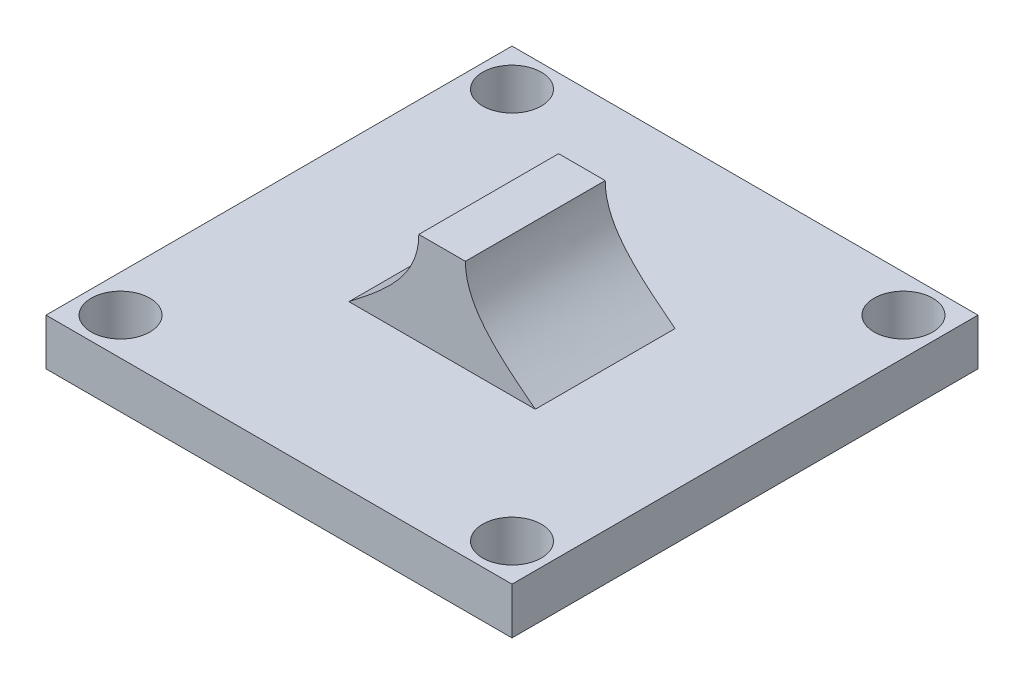
SolidWorks part; units mm, degrees
ref_plane "Front Plane" through (0, 0, 0) normal (0, 0, 1) x (1, 0, 0)
ref_plane "Top Plane" through (0, 0, 0) normal (0, 1, 0) x (1, 0, 0)
ref_plane "Right Plane" through (0, 0, 0) normal (1, 0, 0) x (0, 0, -1)
sketch "Sketch1" plane through (0, 0, 0) normal (0, 1, 0) x (1, 0, 0)
  line L1 (-25, 25) -> (25, 25)
  line L2 (-25, 25) -> (-25, -25)
  line L3 (-25, -25) -> (25, -25)
  line L4 (25, 25) -> (25, -25)
  line L5 (-25, 25) -> (25, -25) construction
  line L6 (-25, -25) -> (25, 25) construction
  point P0 (0, 0)
  dimension "D1" = 50
  dimension "D2" = 50
extrude "Boss-Extrude1" add sketch "Sketch1" along normal blind 5
sketch "Sketch2" plane through (0, 5, 0) normal (0, 1, 0) x (1, 0, 0)
  line L1 (-10, 7.5) -> (10, 7.5)
  line L2 (-10, 7.5) -> (-10, -7.5)
  line L3 (-10, -7.5) -> (10, -7.5)
  line L4 (10, 7.5) -> (10, -7.5)
  line L5 (-10, 7.5) -> (10, -7.5) construction
  line L6 (-10, -7.5) -> (10, 7.5) construction
  point P0 (0, 0)
  dimension "D1" = 20
  dimension "D2" = 15
ref_plane "Plane1" through (0, 15, 0) normal (0, 1, 0) x (1, 0, 0)
sketch "Sketch3" plane through (0, 15, 0) normal (0, 1, 0) x (1, 0, 0)
  line L0 (-10, -7.5) -> (10, -7.5) construction
  line L1 (-2.5, 7.5) -> (2.5, 7.5)
  line L2 (-2.5, 7.5) -> (-2.5, -7.5)
  line L3 (-2.5, -7.5) -> (2.5, -7.5)
  line L4 (2.5, 7.5) -> (2.5, -7.5)
  line L5 (-2.5, 7.5) -> (2.5, -7.5) construction
  line L6 (-2.5, -7.5) -> (2.5, 7.5) construction
  point P0 (0, 0)
  dimension "D1" = 5
loft "Loft1" add profiles "Sketch3", "Sketch2" start constraint normal to profile start tangent length 1 connector at (-2.5, 15, -7.5) connector at (-10, 5, -7.5)
sketch "Sketch7" plane through (0, 0, 0) normal (0, -1, 0) x (-1, 0, 0)
  line L0 (25, 25) -> (25, -25) construction
  line L1 (25, -25) -> (-25, -25) construction
  line L2 (-25, -25) -> (-25, 25) construction
  line L3 (-25, 25) -> (25, 25) construction
  circle A0 centre (21, -21) radius 3.15
  circle A1 centre (-21, -21) radius 3.15
  circle A2 centre (-21, 21) radius 3.15
  circle A3 centre (21, 21) radius 3.15
  dimension "D1" = 6.3
  dimension "D2" = 6.3
  dimension "D3" = 6.3
  dimension "D4" = 6.3
  dimension "D5" = 4
  dimension "D6" = 4
  dimension "D7" = 4
  dimension "D8" = 4
  dimension "D9" = 4
  dimension "D10" = 4
  dimension "D11" = 4
  dimension "D12" = 4
extrude "Cut-Extrude1" cut sketch "Sketch7" against normal through all
